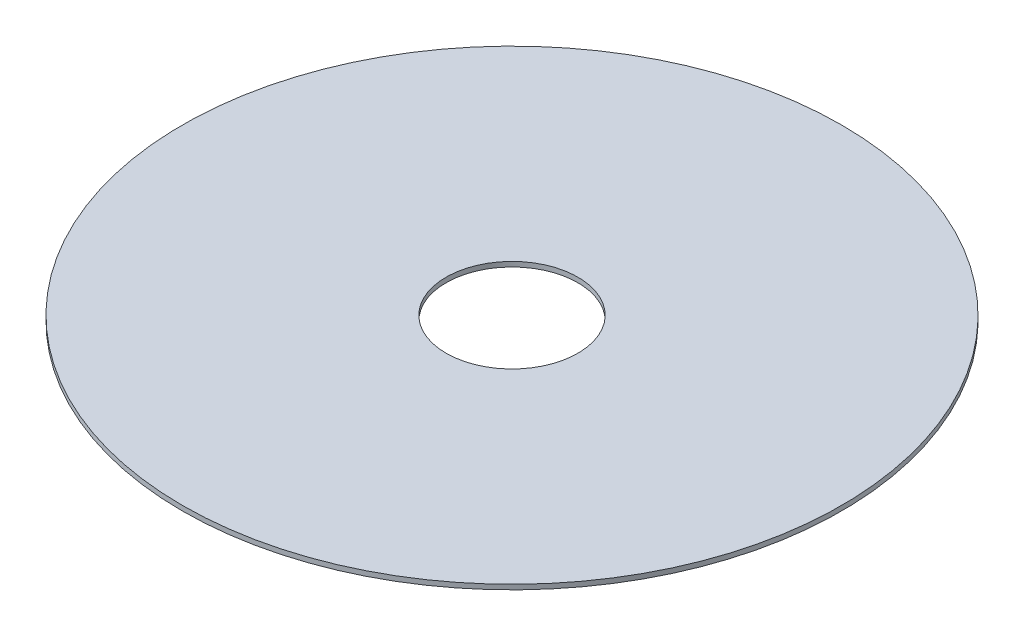
SolidWorks part; units mm, degrees
ref_plane "Front Plane" through (0, 0, 0) normal (0, 0, 1) x (1, 0, 0)
ref_plane "Top Plane" through (0, 0, 0) normal (0, 1, 0) x (1, 0, 0)
ref_plane "Right Plane" through (0, 0, 0) normal (1, 0, 0) x (0, 0, -1)
sketch "Sketch1" plane through (0, 0, 0) normal (0, 1, 0) x (1, 0, 0)
  circle A0 centre (0, 0) radius 50
  circle A1 centre (0, 0) radius 10
base flange "Base-Flange1" sketch "Sketch1" thickness 0.7366 reverse thickness direction no parameters "D1"=0.7366
sketch "Bend-Lines1" plane through (0, 0, 0) normal (0, 1, 0) x (1, 0, 0)
sketch "Bounding-Box1" plane through (0, 0, 0) normal (0, 1, 0) x (1, 0, 0)
sheet metal parameters "Sheet-Metal1" thickness 0.7366 parameters "D1"=0.7366
flat pattern "Flat-Pattern1" [suppressed]
sketch "Bend-Lines2" plane through (0, 0, 0) normal (0, 1, 0) x (1, 0, 0)
sketch "Bounding-Box2" [suppressed] plane through (0, 0, 0) normal (0, 1, 0) x (1, 0, 0)
